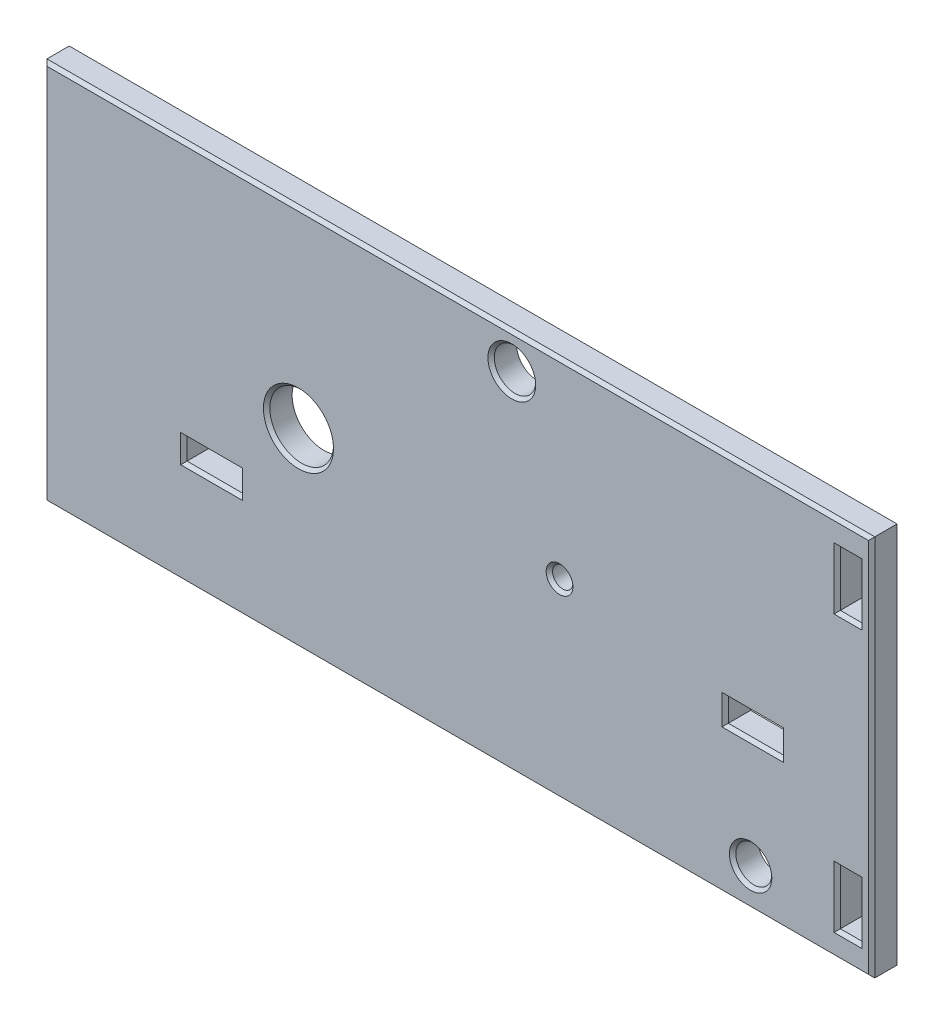
SolidWorks part; units mm, degrees
ref_plane "Front Plane" through (0, 0, 0) normal (0, 0, 1) x (1, 0, 0)
ref_plane "Top Plane" through (0, 0, 0) normal (0, 1, 0) x (1, 0, 0)
ref_plane "Right Plane" through (0, 0, 0) normal (1, 0, 0) x (0, 0, -1)
sketch "Sketch1" plane through (0, 0, 0) normal (0, 0, 1) x (1, 0, 0)
  line L0 (-55.3, -10.3) -> (-55.3, -13.7)
  line L1 (-86, -30) -> (44, -30)
  line L2 (-86, -30) -> (-86, 30)
  line L3 (-86, 30) -> (44, 30)
  line L4 (44, -30) -> (44, 30)
  line L5 (-64, -10.3) -> (-55.3, -10.3)
  line L6 (-64, -10.3) -> (-64, -13.7)
  line L7 (-64, -13.7) -> (-55.3, -13.7)
  line L13 (29.7, -5) -> (21, -5) construction
  line L14 (-55.3, -12) -> (-64, -12) construction
  line L15 (-59.65, -10.3) -> (-59.65, -13.7) construction
  line L16 (40.3, 26) -> (40.3, 17.3) construction
  line L17 (38.6, 26) -> (42, 26)
  line L18 (38.6, 26) -> (38.6, 17.3)
  line L19 (38.6, 17.3) -> (42, 17.3)
  line L20 (42, 26) -> (42, 17.3)
  line L21 (38.6, -17.3) -> (42, -17.3)
  line L22 (38.6, -17.3) -> (38.6, -26)
  line L23 (38.6, -26) -> (42, -26)
  line L24 (42, -17.3) -> (42, -26)
  line L25 (42, 21.65) -> (38.6, 21.65) construction
  line L26 (40.3, -17.3) -> (40.3, -26) construction
  line L27 (42, -21.65) -> (38.6, -21.65) construction
  line L28 (21, -3.15) -> (29.7, -3.15)
  line L29 (21, -3.15) -> (21, -6.85)
  line L30 (21, -6.85) -> (29.7, -6.85)
  line L31 (29.7, -3.15) -> (29.7, -6.85)
  line L32 (25.35, -6.85) -> (25.35, -3.15) construction
  circle A2 centre (-46, 0) radius 5
  circle A3 centre (-12.5, 24.5) radius 3.25
  circle A4 centre (25, -24) radius 2.83
  circle A5 centre (-5, 0) radius 1.6
  point P1 (0, 0)
  point P24 (-86, 0)
  dimension "D10" = 6.5
  dimension "D14" = 5.66
  dimension "D21" = 10
  dimension "D2" = 60
  dimension "D4" = 130
  dimension "D6" = 8.7
  dimension "D8" = 3.4
  dimension "D12" = 111
  dimension "D19" = 24.5
  dimension "D13" = 24
  dimension "D5" = 40
  dimension "D7" = 33.5
  dimension "D9" = 7.5
  dimension "D11" = 26.35
  dimension "D15" = 126.3
  dimension "D17" = 21.65
  dimension "D18" = 21.65
  dimension "D16" = 85
  dimension "D3" = 5
  dimension "D20" = 12
extrude "Boss-Extrude1" add sketch "Sketch1" along normal mid plane 4
sketch "Sketch2" plane through (0, 0, 2) normal (0, 0, 1) x (1, 0, 0)
  line L0 (40.3, 26) -> (40.3, 17.3) construction
  line L1 (42, 21.65) -> (38.6, 21.65) construction
  line L2 (40.3, -17.3) -> (40.3, -26) construction
  line L3 (42, -17.3) -> (38.6, -17.3) construction
  line L4 (38.6, -26) -> (42, -26) construction
  line L5 (38.6, -21.65) -> (42, -21.65) construction
  line L6 (38.6, -17.3) -> (38.6, -26) construction
  line L7 (42, -26) -> (42, -17.3) construction
sketch "Sketch4" plane through (0, 0, -2) normal (0, 0, -1) x (-1, 0, 0)
  line L0 (59.65, -10.3) -> (59.65, -13.7) construction
  line L1 (55.3, -12) -> (64, -12) construction
  line L2 (-29.7, -5) -> (-21, -5) construction
  line L3 (-29.7, -6.85) -> (-29.7, -3.15) construction
  line L4 (-21, -3.15) -> (-21, -6.85) construction
  line L5 (-25.35, -3.15) -> (-25.35, -6.85) construction
  line L6 (-29.7, -3.15) -> (-21, -3.15) construction
  line L7 (-21, -6.85) -> (-29.7, -6.85) construction
chamfer "Chamfer1" distance 0.5 angle 45 24 edges at (40.3, -26, 2) (42, -21.65, 2) (40.3, -17.3, 2) (38.6, -21.65, 2) (-3.4, 0, 2) (27.83, -24, 2) (-41, 0, 2) (-9.25, 24.5, 2) (-59.65, -13.7, 2) (-55.3, -12, 2) (-59.65, -10.3, 2) (-64, -12, 2) (-21, -30, 2) (-86, 0, 2) (-21, 30, 2) (44, 0, 2) (25.35, -6.85, 2) (29.7, -5, 2) (25.35, -3.15, 2) (21, -5, 2) (40.3, 17.3, 2) (42, 21.65, 2) (40.3, 26, 2) (38.6, 21.65, 2)
equation "\"padding\"=4"
equation "\"hole_width\"=3.4"
equation "\"hole_height\"=8.7"
equation "\"back_boost\"= 7"
equation "\"D5@Sketch1\"=33+\"back_boost\""
equation "\"D12@Sketch1\"=104+\"back_boost\""
equation "\"D15@Sketch1\"=119.30mm+\"back_boost\""
equation "\"D11@Sketch1\"=\"back_boost\"+19.35mm"
equation "\"D4@Sketch1\"=\"back_boost\"+123.00mm"
equation "\"pin_hole_height\"=9"
equation "\"pin_hole_width\"=3.65"
